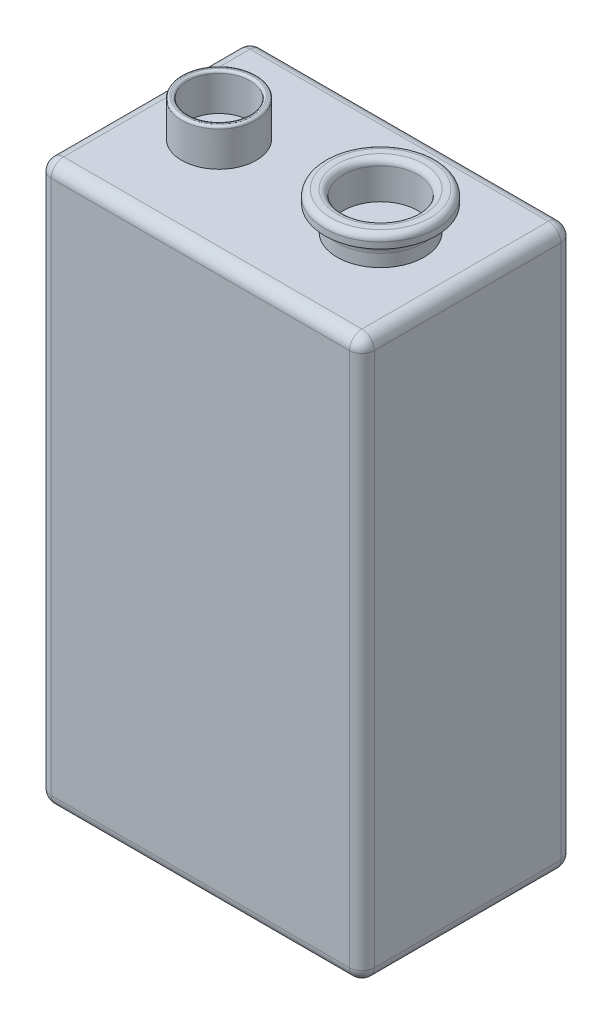
SolidWorks part; units mm, degrees
ref_plane "Front Plane" through (0, 0, 0) normal (0, 0, 1) x (1, 0, 0)
ref_plane "Top Plane" through (0, 0, 0) normal (0, 1, 0) x (1, 0, 0)
ref_plane "Right Plane" through (0, 0, 0) normal (1, 0, 0) x (0, 0, -1)
sketch "Sketch1" plane through (0, 0, 0) normal (0, 1, 0) x (1, 0, 0)
  line L1 (13, 8.5) -> (-13, 8.5)
  line L2 (13, 8.5) -> (13, -8.5)
  line L3 (13, -8.5) -> (-13, -8.5)
  line L4 (-13, 8.5) -> (-13, -8.5)
  line L5 (13, 8.5) -> (-13, -8.5) construction
  line L6 (13, -8.5) -> (-13, 8.5) construction
  point P0 (0, 0)
  dimension "D1" = 26
  dimension "D2" = 17
extrude "Boss-Extrude1" add sketch "Sketch1" along normal blind 45
fillet "Fillet1" radius 1 12 edges at (0, 0, 8.5) (13, 0, 0) (0, 0, -8.5) (-13, 0, 0) (0, 45, -8.5) (13, 45, 0) (0, 45, 8.5) (-13, 45, 0) (-13, 22.5, -8.5) (13, 22.5, -8.5) (-13, 22.5, 8.5) (13, 22.5, 8.5)
sketch "Sketch2" plane through (0, 45, 0) normal (0, 1, 0) x (1, 0, 0)
  line L0 (-13, -7.5) -> (-13, 7.5) construction
  circle A0 centre (-7, 0) radius 3
  circle A1 centre (-7, 0) radius 2.5
  point P3 (-13, 0)
  dimension "D1" = 6
  dimension "D2" = 5
  dimension "D3" = 6
extrude "Boss-Extrude2" add sketch "Sketch2" along normal blind 3
sketch "Sketch3" plane through (0, 45, 0) normal (0, 1, 0) x (1, 0, 0)
  line L0 (12, -7.5) -> (12, 7.5) construction
  circle A0 centre (6, 0) radius 3.5
  circle A1 centre (6, 0) radius 3
  point P3 (12, 0)
  dimension "D1" = 7
  dimension "D2" = 6
  dimension "D3" = 6
extrude "Boss-Extrude3" add sketch "Sketch3" along normal blind 2
sketch "Sketch4" plane through (0, 47, 0) normal (0, 1, 0) x (1, 0, 0)
  circle A0 centre (6, 0) radius 3
  circle A1 centre (6, 0) radius 4.5
  dimension "D1" = 9
extrude "Boss-Extrude4" add sketch "Sketch4" along normal blind 1
fillet "Fillet4" radius 1 1 edges at (6, 47, 3.5)
fillet "Fillet5" radius 0.5 2 edges at (6, 48, 3) (6, 48, 4.5)
fillet "Fillet6" radius 0.2 2 edges at (-7, 48, 2.5) (-7, 48, 3)
